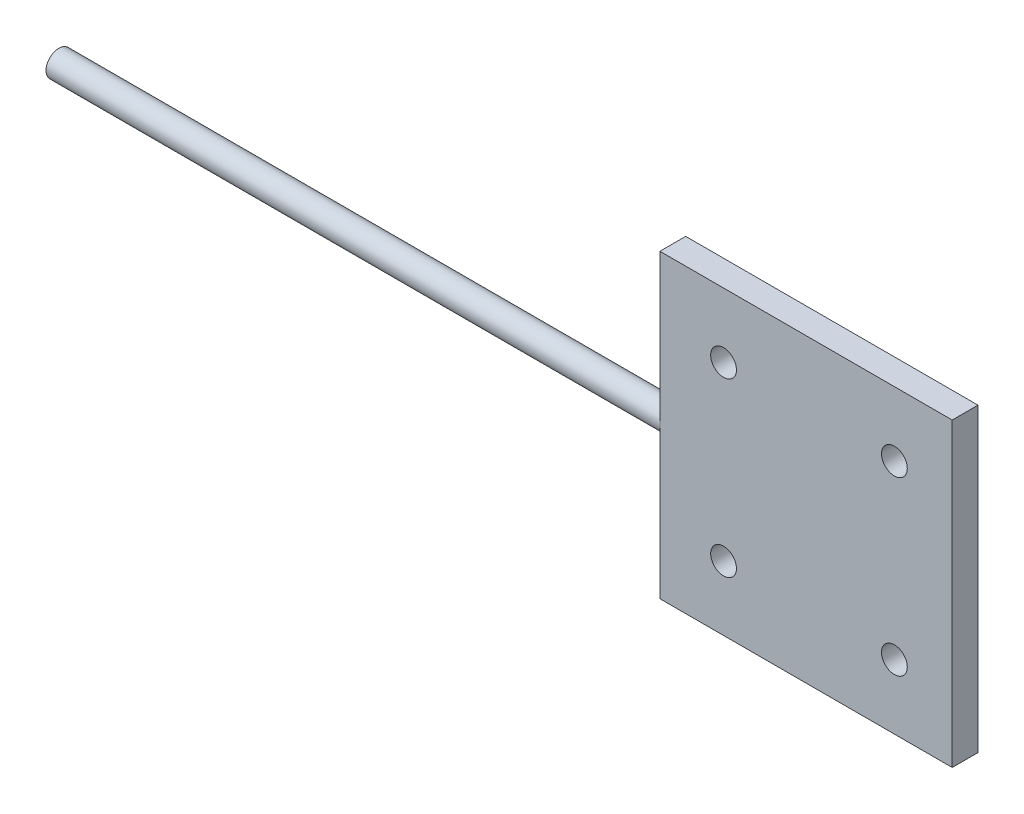
SolidWorks part; units mm, degrees
ref_plane "前视基准面" through (0, 0, 0) normal (0, 0, 1) x (1, 0, 0)
ref_plane "上视基准面" through (0, 0, 0) normal (0, 1, 0) x (1, 0, 0)
ref_plane "右视基准面" through (0, 0, 0) normal (1, 0, 0) x (0, 0, -1)
sketch "草图1" plane through (0, 0, 0) normal (0, 0, 1) x (1, 0, 0)
  line L1 (17, -17.5) -> (-17, -17.5)
  line L2 (17, -17.5) -> (17, 17.5)
  line L3 (17, 17.5) -> (-17, 17.5)
  line L4 (-17, -17.5) -> (-17, 17.5)
  line L5 (17, -17.5) -> (-17, 17.5) construction
  line L6 (17, 17.5) -> (-17, -17.5) construction
  point P0 (0, 0)
  dimension "D1" = 35
  dimension "D2" = 34
extrude "凸台-拉伸1" add sketch "草图1" along normal blind 3
sketch "草图7" plane through (0, 0, 3) normal (0, 0, 1) x (1, 0, 0)
  circle A0 centre (10.2752, 10) radius 1.5
  circle A1 centre (10.2752, -10) radius 1.5
  circle A2 centre (-9.5936, 10) radius 1.5
  circle A3 centre (-9.5936, -10) radius 1.5
  dimension "D1" = 10
  dimension "D2" = 10
  dimension "D3" = 10
  dimension "D5" = 3
  dimension "D4" = 10
extrude "切除-拉伸1" cut sketch "草图7" against normal blind 10
sketch "草图8" plane through (-17, 0, 0) normal (-1, 0, 0) x (0, 0, 1)
  line L0 (0, 0) -> (3, 0) construction
  line L1 (0, 17.5) -> (0, -17.5) construction
  line L2 (3, 17.5) -> (3, -17.5) construction
  circle A0 centre (1.5, 0) radius 1.5
  dimension "D1" = 3
extrude "凸台-拉伸2" add sketch "草图8" along normal blind 71.4
